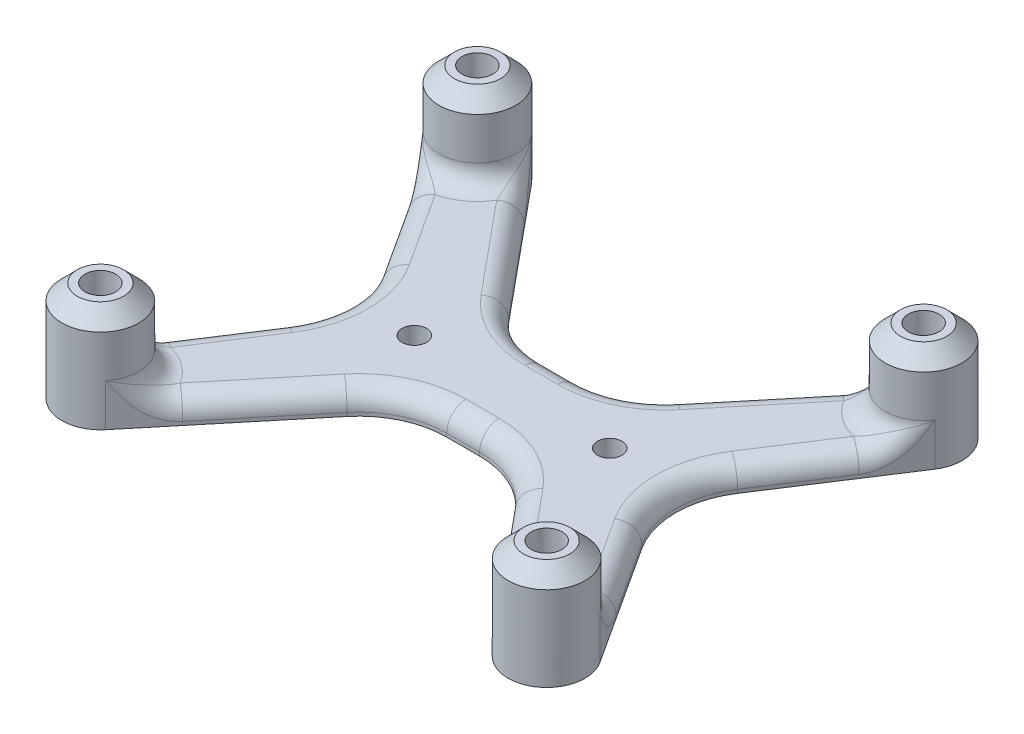
SolidWorks part; units mm, degrees
ref_plane "Front Plane" through (0, 0, 0) normal (0, 0, 1) x (1, 0, 0)
ref_plane "Top Plane" through (0, 0, 0) normal (0, 1, 0) x (1, 0, 0)
ref_plane "Right Plane" through (0, 0, 0) normal (1, 0, 0) x (0, 0, -1)
sketch "Sketch1" plane through (0, 0, 0) normal (0, 1, 0) x (1, 0, 0)
  line L0 (-7.5163, 6.35) -> (7.5163, 6.35)
  line L1 (-29, -24.5) -> (29, -24.5) construction
  line L2 (-29, -24.5) -> (-29, 24.5) construction
  line L3 (-29, 24.5) -> (29, 24.5) construction
  line L4 (29, -24.5) -> (29, 24.5) construction
  line L5 (-29, -24.5) -> (29, 24.5) construction
  line L6 (-29, 24.5) -> (29, -24.5) construction
  line L7 (-19.05, -6.35) -> (19.05, -6.35) construction
  line L8 (-19.05, -6.35) -> (-19.05, 6.35) construction
  line L9 (-19.05, 6.35) -> (19.05, 6.35) construction
  line L10 (19.05, -6.35) -> (19.05, 6.35) construction
  line L11 (-19.05, -6.35) -> (19.05, 6.35) construction
  line L12 (-19.05, 6.35) -> (19.05, -6.35) construction
  line L13 (7.5163, 6.35) -> (25.1456, 27.6849)
  line L14 (19.05, 0) -> (33.1932, 21.7766)
  line L15 (19.05, 0) -> (33.1932, -21.7766)
  line L16 (25.1456, -27.6849) -> (7.5163, -6.35)
  line L17 (7.5163, -6.35) -> (-7.5163, -6.35)
  line L18 (-7.5163, -6.35) -> (-25.1456, -27.6849)
  line L19 (-19.05, 0) -> (-33.1932, -21.7766)
  line L20 (-19.05, 0) -> (-33.1932, 21.7766)
  line L21 (-25.1456, 27.6849) -> (-7.5163, 6.35)
  circle A0 centre (-29, -24.5) radius 5
  circle A1 centre (29, -24.5) radius 5
  circle A2 centre (29, 24.5) radius 5
  circle A3 centre (-29, 24.5) radius 5
  point P0 (0, 0)
  point P6 (0, 0)
  dimension "D5" = 10
  dimension "D6" = 10
  dimension "D7" = 10
  dimension "D8" = 10
  dimension "D1" = 12.7
  dimension "D2" = 38.1
  dimension "D3" = 58
  dimension "D4" = 49
extrude "Boss-Extrude1" add sketch "Sketch1" along normal blind 3 contours A0 | A3 L20 L19 A0 L18 L17 L16 A1 L15 L14 A2 L13 L0 L21 | A3 | A2 | A1 region at (0, 0, 0) region at (-29, 0, -24.5) region at (29, 0, -24.5) region at (-29, 0, 24.5) region at (29, 0, 24.5)
sketch "Sketch2" plane through (0, 3, 0) normal (0, 1, 0) x (1, 0, 0)
  circle A0 centre (-29, -24.5) radius 5
  circle A1 centre (29, -24.5) radius 5
  circle A2 centre (29, 24.5) radius 5
  circle A3 centre (-29, 24.5) radius 5
extrude "Boss-Extrude2" add sketch "Sketch2" along normal blind 10
sketch "Sketch3" plane through (0, 13, 0) normal (0, 1, 0) x (1, 0, 0)
  circle A0 centre (-29, -24.5) radius 2
  circle A1 centre (-29, 24.5) radius 2
  circle A2 centre (29, 24.5) radius 2
  circle A3 centre (29, -24.5) radius 2
  dimension "D1" = 4
  dimension "D2" = 4
  dimension "D3" = 4
  dimension "D4" = 4
extrude "Cut-Extrude1" cut sketch "Sketch3" against normal blind 4.8
fillet "Fillet2" radius 11.43 4 edges at (7.5163, 1.5, -6.35) (-7.5163, 1.5, -6.35) (7.5163, 1.5, 6.35) (-7.5163, 1.5, 6.35)
fillet "Fillet3" radius 11.43 2 edges at (-19.05, 1.5, 0) (19.05, 1.5, 0)
fillet "Fillet4" radius 2.54 4 edges at (-26.041, 3, 20.4696) (26.041, 3, 20.4696) (26.041, 3, -20.4696) (-26.041, 3, -20.4696)
fillet "Fillet5" radius 2.54 24 edges at (31.0686, 3.3005, 18.5052) (26.6063, 3, 11.6346) (31.0686, 3.3005, -18.5052) (26.6063, 3, -11.6346) (-22.6609, 3.3005, 24.6779) (-16.2478, 3, 16.9168) (-7.0034, 3, 7.4392) (0, 3, 6.35) (22.6609, 3.3005, 24.6779) (16.2478, 3, 16.9168) (-31.0686, 3.3005, -18.5052) (-26.6063, 3, -11.6346) (-31.0686, 3.3005, 18.5052) (-26.6063, 3, 11.6346) (-22.6609, 3.3005, -24.6779) (-16.2478, 3, -16.9168) (-7.0034, 3, -7.4392) (0, 3, -6.35) (7.0034, 3, -7.4392) (22.6609, 3.3005, -24.6779) (21.2491, 3, 0) (7.0034, 3, 7.4392) (-21.2491, 3, 0) (16.2478, 3, -16.9168)
sketch "Sketch4" plane through (0, 3, 0) normal (0, 1, 0) x (1, 0, 0)
  circle A0 centre (-12.7, 0) radius 1.5875
  circle A1 centre (12.7, 0) radius 1.5875
  dimension "D1" = 3.175
  dimension "D3" = 3.175
  dimension "D2" = 12.7
  dimension "D4" = 12.7
extrude "Cut-Extrude2" cut sketch "Sketch4" against normal through all
chamfer "Chamfer1" distance 2 angle 45 4 edges at (-29, 13, 29.5) (-29, 13, -19.5) (29, 13, -19.5) (29, 13, 29.5)
sketch "Sketch5" plane through (0, 8.2, 0) normal (0, 1, 0) x (1, 0, 0)
  circle A0 centre (-29, -24.5) radius 1.35
  dimension "D1" = 2.7
extrude "Cut-Extrude3" cut sketch "Sketch5" against normal through all
mirror "Mirror1" about plane through (0, 0, 0) normal (1, 0, 0) of "Cut-Extrude3" second plane through (0, 0, 0) second plane normal (0, 0, 1)
